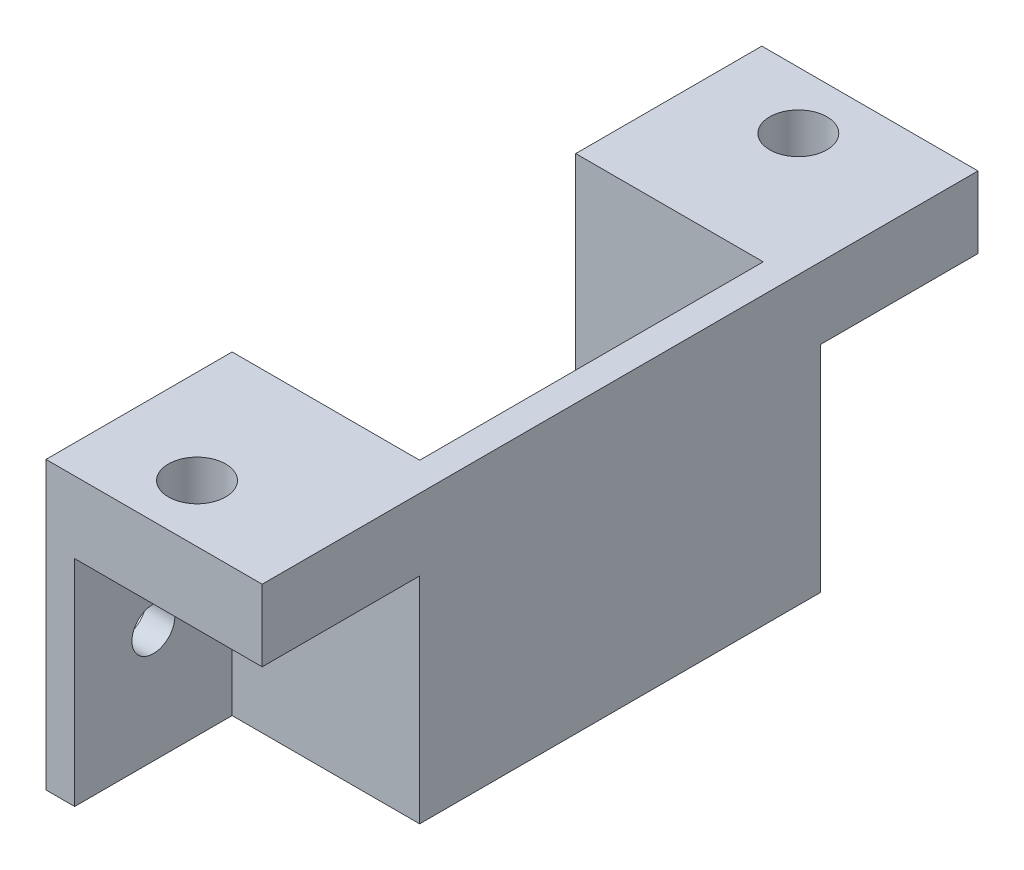
SolidWorks part; units mm, degrees
ref_plane "Płaszczyzna przednia" through (0, 0, 0) normal (0, 0, 1) x (1, 0, 0)
ref_plane "Płaszczyzna górna" through (0, 0, 0) normal (0, 1, 0) x (1, 0, 0)
ref_plane "Płaszczyzna prawa" through (0, 0, 0) normal (1, 0, 0) x (0, 0, -1)
sketch "Sketch1" plane through (0, 0, 0) normal (0, 1, 0) x (1, 0, 0)
  line L1 (15.1, 14) -> (15.1, 25)
  line L3 (0, 14) -> (2, 14)
  line L4 (0, 14) -> (0, 25)
  line L5 (0, 25) -> (2, 25)
  line L6 (0, 14) -> (15.1, 14)
  line L7 (0, 12) -> (13.1, 12)
  line L8 (0, 12) -> (0, -12)
  line L9 (0, -12) -> (13.1, -12)
  line L10 (13.1, 12) -> (13.1, -12)
  line L11 (15.1, 14) -> (15.1, -14)
  line L12 (0, -14) -> (15.1, -14)
  line L13 (0, 14) -> (0, -14)
  line L14 (2, 14) -> (2, 25)
  line L15 (0, -14) -> (2, -14)
  line L16 (0, -14) -> (0, -25)
  line L17 (0, -25) -> (2, -25)
  line L18 (2, -14) -> (2, -25)
  line L19 (15.1, 25) -> (2, 25)
  line L20 (6.55, 29.9244) -> (6.55, -34.5201) construction
  line L21 (15.1, -14) -> (15.1, -25)
  line L22 (15.1, -25) -> (2, -25)
  line L23 (-22.5276, 0) -> (51.0243, 0) construction
  circle A0 centre (6.55, 21) radius 2
  circle A1 centre (6.55, -21) radius 2
  point P7 (0, 0)
  point P26 (0, 0)
  point P28 (0, 0)
  point P29 (6.55, 29.9244)
  point P30 (6.55, -34.5201)
  point P31 (6.55, 19.6577)
  point P32 (6.55, 12)
  dimension "D1" = 4
  dimension "D2" = 9
  dimension "D8" = 2
  dimension "D9" = 2
  dimension "D3" = 4
  dimension "D5" = 13.1
  dimension "D6" = 24
  dimension "D7" = 2
  dimension "D4" = 9
  dimension "D10" = 50
extrude "Boss-Extrude1" add sketch "Sketch1" along normal blind 20 contours L3 L13 L7 L10 L9 L12 L11 L6 | L3 L14 L5 L4 | L18 L12 L16 L17 region at (14.7819, 0, 0) region at (1, 0, -19.5) region at (1, 0, 19.5)
sketch "Sketch4" plane through (2, 0, 0) normal (1, 0, 0) x (0, 0, -1)
  line L0 (-19.5, 20) -> (-19.5, 0) construction
  line L1 (-14, 20) -> (-25, 20) construction
  line L2 (-14, 0) -> (-25, 0) construction
  line L3 (14, 20) -> (25, 20) construction
  circle A0 centre (-19.5, 8) radius 1.5
  circle A1 centre (19.5, 8) radius 1.5
  point P2 (19.5, 10)
  point P11 (0, 0)
  point P12 (0, 0)
  point P15 (19.5, 20)
  point P16 (-19.5, 7.9807)
  dimension "D1" = 3
  dimension "D2" = 3
  dimension "D3" = 8
extrude "Cut-Extrude1" cut sketch "Sketch4" along normal through all both and the other way through all
extrude "Boss-Extrude2" add sketch "Sketch1<31>" against normal blind 5 from surface contours A1 L20 L22 L21 L12 | L20 A1 L12 L18 L22 | L19 L20 A0 L6 L1 | L20 L19 L14 L6 A0 region at (8.7411, 0, -19.3567) region at (8.7411, 0, 19.3567) starting at face at (5.3667, 20, 0)
sketch "Sketch1<31>" plane through (0, 0, 0) normal (0, 1, 0) x (1, 0, 0) same geometry as "Sketch1"
